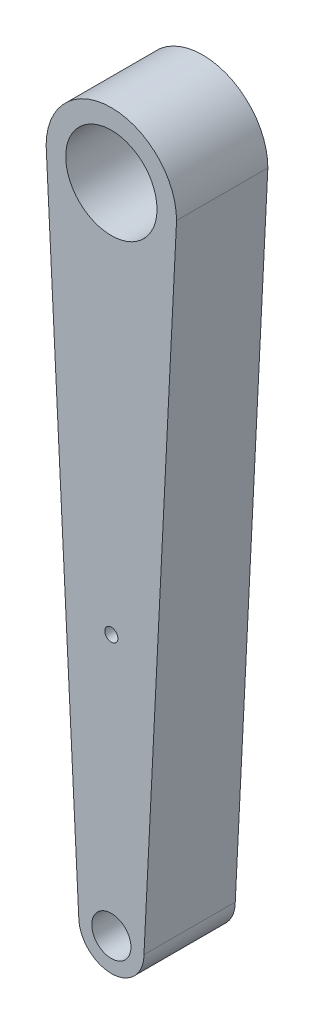
SolidWorks part; units mm, degrees
ref_plane "Front Plane" through (0, 0, 0) normal (0, 0, 1) x (1, 0, 0)
ref_plane "Top Plane" through (0, 0, 0) normal (0, 1, 0) x (1, 0, 0)
ref_plane "Right Plane" through (0, 0, 0) normal (1, 0, 0) x (0, 0, -1)
sketch "Sketch1" plane through (0, 0, 0) normal (0, 0, 1) x (1, 0, 0)
  line L0 (5, 30) -> (2.5, -20)
  line L1 (-2.5, -20) -> (-5, 30)
  arc A0 (4.9751, 29.5012) -> (-4.9751, 29.5012) centre (0, 30) ccw
  arc A1 (-2.5, -20) -> (2.5, -20) centre (0, -20) ccw
  circle A2 centre (0, 30) radius 3.5
  circle A3 centre (0, -20) radius 1.5
  circle A4 centre (0, 0) radius 0.5
  dimension "D3" = 5
  dimension "D4" = 10
  dimension "D5" = 3
  dimension "D6" = 7
  dimension "D7" = 1
  dimension "D1" = 50
  dimension "D2" = 20
extrude "Boss-Extrude1" add sketch "Sketch1" along normal blind 7 contours L1 A1 L0 A0 A3 A2 region at (0, 7.831, 0)
extrude "Boss-Extrude2" add sketch "Sketch1<4>" along normal blind 5 contours A4
sketch "Sketch1<4>" plane through (0, 0, 0) normal (0, 0, 1) x (1, 0, 0) same geometry as "Sketch1"
extrude "Cut-Extrude3" cut sketch "Sketch1<5>" along normal blind 17 contours A4
sketch "Sketch1<5>" plane through (0, 0, 0) normal (0, 0, 1) x (1, 0, 0) same geometry as "Sketch1"
